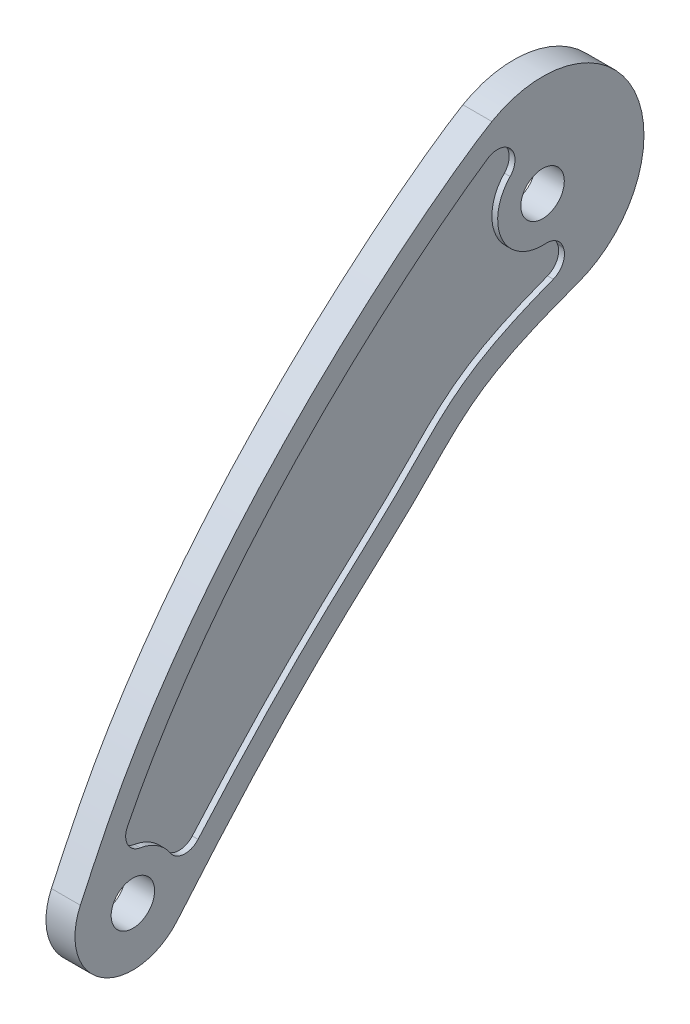
SolidWorks part; units mm, degrees
note: '?' marks a value the reader was unsure of.
ref_plane "Front Plane" through (0, 0, 0) normal (0, 0, 1) x (1, 0, 0)
ref_plane "Top Plane" through (0, 0, 0) normal (0, 1, 0) x (1, 0, 0)
ref_plane "Right Plane" through (0, 0, 0) normal (1, 0, 0) x (0, 0, -1)
sketch "Sketch1" plane through (0, 0, 0) normal (1, 0, 0) x (0, 0, -1)
  line L0 (0, 0) -> (-141.4214, -141.4214) construction
  line L1 (0, 0) -> (0, 2.0242) construction
  line L2 (-141.4214, -141.4214) -> (-159.5475, -132.969) construction
  line L3 (-141.4214, -141.4214) -> (-126.1005, -154.2771) construction
  line L4 (-17.5, 30.3109) -> (0, 0) construction
  line L5 (0, 0) -> (11.9707, -32.8892) construction
  line L7 (-147.0782, -107.4802) -> (-127.2792, -127.2792) construction
  line L9 (-36.7696, -62.2254) -> (-49.4975, -49.4975) construction
  arc A0 (11.9707, -32.8892) -> (-17.5, 30.3109) centre (0, 0) ccw
  arc A1 (-159.5475, -132.969) -> (-126.1005, -154.2771) centre (-141.4214, -141.4214) ccw
  spline S0 degree 3 poles (-17.5, 30.3109) (-34.322, 20.5987) (-116.724, -40.4103) (-156.3138, -126.0342) (-159.5475, -132.969) knots 0 0 0 0 0.889912 1 1 1 1
  spline S1 degree 3 poles (-126.1005, -154.2771) (-80.6418, -100.1015) (-58.2293, -84.7195) (-25.9191, -50.7903) (-14.885, -42.6639) (11.9707, -32.8892) knots 0 0 0 0 0.511217 0.600271 0.890535 0.890535 0.890535 0.890535
  dimension "D2" = 35
  dimension "D3" = 20
  dimension "D1" = 200
  dimension "D4" = 135
  dimension "D5" = 110
  dimension "D6" = 85
  dimension "D7" = 105
  dimension "D8" = 65
  dimension "D9" = 20
  dimension "D11" = 28
  dimension "D15" = 70
  dimension "D16" = 18
extrude "Boss-Extrude1" add sketch "Sketch1" along normal blind 10
sketch "Sketch2" plane through (10, 0, 0) normal (1, 0, 0) x (0, 0, -1)
  circle A0 centre (0, 0) radius 7.5
  circle A1 centre (-141.4214, -141.4214) radius 7.5
  dimension "D1" = 15
  dimension "D2" = 15
extrude "Cut-Extrude1" cut sketch "Sketch2" against normal through all both and the other way through all
ref_axis "Axis1" through (5, -134.981, 155.2327) along (0, 0.4226, 0.9063)?
sketch "Sketch8" plane through (10, 0, 0) normal (1, 0, 0) x (0, 0, -1)
  line L0 (0, 0) -> (-7.75, 13.4234) construction
  line L1 (-7.75, 13.4234) -> (-13.5, 23.3827)
  line L2 (0, 0) -> (5.3013, -14.5652) construction
  line L3 (5.3013, -14.5652) -> (9.2345, -25.3717)
  circle A3 centre (0, 0) radius 15.5
  circle A4 centre (-141.4214, -141.4214) radius 15.5
  circle A5 centre (-141.4214, -141.4214) radius 7.5 construction
  circle A7 centre (0, 0) radius 7.5 construction
  spline S2 degree 3 poles (-2719.2709, -1271.2912) (-155.4681, -99.4448) (20.3431, 44.3844) (-15.9308, 21.9102) (-16.6723, 21.4387) (-19.0961, 19.8585) (-20.9775, 18.5845) (-27.2868, 14.1472) (-32.3806, 10.3682) (-49.5033, -3.1775) (-63.3775, -15.1566) (-91.9648, -43.804) (-106.6789, -60.4756) (-126.3733, -88.0658) (-132.5423, -97.6922) (-138.7623, -108.9128) (-139.4433, -110.1646) (-140.785, -112.6802) (-141.4475, -113.947) (-143.4037, -117.7494) (-144.6658, -120.2867) (-147.0748, -125.2351) (-148.2218, -127.6463) (-187.8679, -211.891) (-134.2281, -131.3623) (531.9018, 2784.4692) knots -1.63728 -1.63728 -1.63728 -1.63728 0.03125 0.03125 0.0625 0.0625 0.125 0.125 0.25 0.25 0.5 0.5 0.75 0.75 0.875 0.875 0.890625 0.890625 0.90625 0.90625 0.9375 0.9375 0.96875 0.96875 2.089576 2.089576 2.089576 2.089576 only from (-13.5, 23.3827) to (-152.297, -136.3499)
  spline S3 degree 3 poles (-13.5, 23.3827) (-14.0043, 23.0915) (-14.597, 22.7366) (-15.9308, 21.9102) (-16.6723, 21.4387) (-19.0961, 19.8585) (-20.9775, 18.5845) (-27.2868, 14.1472) (-32.3806, 10.3682) (-49.5033, -3.1775) (-63.3775, -15.1566) (-91.9648, -43.804) (-106.6789, -60.4756) (-126.3733, -88.0658) (-132.5423, -97.6922) (-138.7623, -108.9128) (-139.4433, -110.1646) (-140.785, -112.6802) (-141.4475, -113.947) (-143.4037, -117.7494) (-144.6658, -120.2867) (-147.0748, -125.2351) (-148.2218, -127.6463) (-150.3726, -132.2165) (-151.3763, -134.3754) (-152.297, -136.3499) knots 0 0 0 0 0.03125 0.03125 0.0625 0.0625 0.125 0.125 0.25 0.25 0.5 0.5 0.75 0.75 0.875 0.875 0.890625 0.890625 0.90625 0.90625 0.9375 0.9375 0.96875 0.96875 1 1 1 1
  spline S5 degree 3 poles (-1753.2062, -2672.5806) (-516.8022, -646.893) (-214.8373, -238.0865) (-98.0425, -110.3772) (-91.2666, -103.3656) (-79.1556, -91.3361) (-73.8208, -86.3187) (-66.5527, -79.6125) (-64.2527, -77.514) (-59.8394, -73.4774) (-57.7263, -71.5395) (-53.6209, -67.7068) (-51.6286, -65.812) (-49.1666, -63.393) (-48.6766, -62.9076) (-47.6927, -61.9246) (-47.1984, -61.4269) (-45.7106, -59.9211) (-44.7122, -58.9006) (-42.711, -56.8571) (-41.7082, -55.8342) (-39.7035, -53.8153) (-38.7034, -52.821) (-35.6915, -49.9042) (-33.6538, -48.0337) (-29.2621, -44.4001) (-26.91, -42.6408) (-21.6946, -39.2107) (-18.8341, -37.5402) (-12.3847, -34.2017) (-8.7952, -32.532) (89.0719, 8.8347) (447.4195, 80.3094) (2862.9569, 899.1705) knots -1.633951 -1.633951 -1.633951 -1.633951 0.125 0.125 0.25 0.25 0.375 0.375 0.4375 0.4375 0.5 0.5 0.5625 0.5625 0.578125 0.578125 0.59375 0.59375 0.625 0.625 0.65625 0.65625 0.6875 0.6875 0.75 0.75 0.8125 0.8125 0.875 0.875 0.9375 0.9375 2.369685 2.369685 2.369685 2.369685 only from (-132.2288, -149.1348) to (9.2345, -25.3717)
  spline S6 degree 3 poles (-132.2288, -149.1348) (-122.2648, -137.2601) (-113.5412, -127.3242) (-98.0425, -110.3772) (-91.2666, -103.3656) (-79.1556, -91.3361) (-73.8208, -86.3187) (-66.5527, -79.6125) (-64.2527, -77.514) (-59.8394, -73.4774) (-57.7263, -71.5395) (-53.6209, -67.7068) (-51.6286, -65.812) (-49.1666, -63.393) (-48.6766, -62.9076) (-47.6927, -61.9246) (-47.1984, -61.4269) (-45.7106, -59.9211) (-44.7122, -58.9006) (-42.711, -56.8571) (-41.7082, -55.8342) (-39.7035, -53.8153) (-38.7034, -52.821) (-35.6915, -49.9042) (-33.6538, -48.0337) (-29.2621, -44.4001) (-26.91, -42.6408) (-21.6946, -39.2107) (-18.8341, -37.5402) (-12.3847, -34.2017) (-8.7952, -32.532) (-0.6106, -29.0726) (3.9856, -27.2822) (9.2345, -25.3717) knots 0 0 0 0 0.125 0.125 0.25 0.25 0.375 0.375 0.4375 0.4375 0.5 0.5 0.5625 0.5625 0.578125 0.578125 0.59375 0.59375 0.625 0.625 0.65625 0.65625 0.6875 0.6875 0.75 0.75 0.8125 0.8125 0.875 0.875 0.9375 0.9375 1 1 1 1
  point P16 (8.7295, -24.8873)
  point P20 (-13.5, 22.9328)
  dimension "D3" = 8
  dimension "D4" = 8
  dimension "D2" = 8
extrude "Cut-Extrude4" cut sketch "Sketch8" against normal blind 2 contours A4 S6 L3 A3 L1 S3
fillet "Fillet3" radius 6 6 edges at (9, -14.5652, -5.3013) (9, 13.4234, 7.75) tangent propagation no
ref_plane "Plane1" through (5, 0, 0) normal (1, 0, 0) x (0, 0, -1)
mirror "Mirror1" about plane through (5, 0, 0) normal (1, 0, 0) of "Cut-Extrude4"
equation "\"leg_length\"= 200"
equation "\"D1@Sketch1\"=\"leg_length\""
equation "\"D9@Sketch1\"=0.1 * \"leg_length\""
equation "\"D11@Sketch1\"=0.14 * \"leg_length\""
equation "\"D15@Sketch1\"=0.35 * \"leg_length\""
equation "\"D16@Sketch1\"=0.09 * \"leg_length\""
equation "\"link_width\"= 8"
equation "\"D1@Sketch8\"= \"link_width\""
equation "\"D2@Sketch8\"= \"link_width\""
equation "\"D3@Sketch8\"= \"link_width\""
equation "\"D4@Sketch8\"=\"link_width\""
